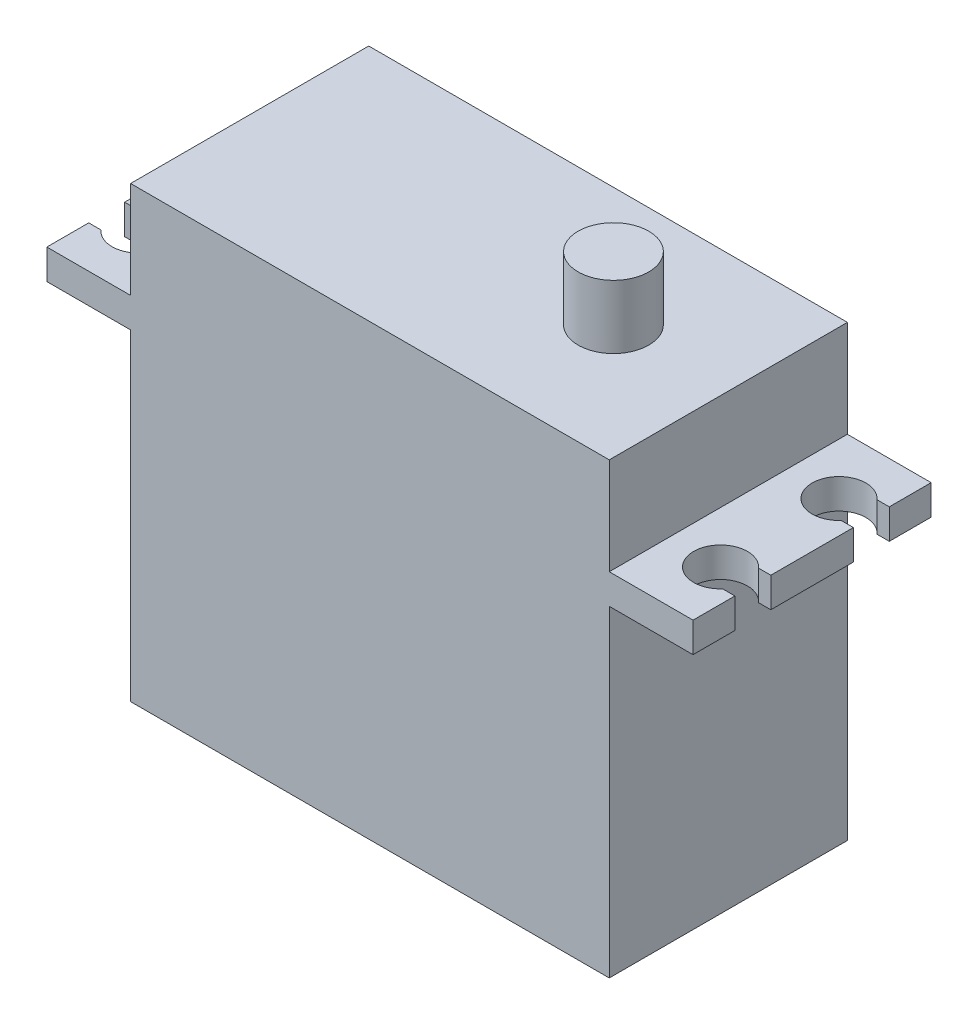
SolidWorks part; units mm, degrees
other "Body"
other "Axis"
material "Nylon 101"
ref_plane "Front Plane" through (0, 0, 0) normal (0, 0, 1) x (1, 0, 0)
ref_plane "Top Plane" through (0, 0, 0) normal (0, 1, 0) x (1, 0, 0)
ref_plane "Right Plane" through (0, 0, 0) normal (1, 0, 0) x (0, 0, -1)
sketch "Sketch1" plane through (0, 0, 0) normal (0, 1, 0) x (1, 0, 0)
  line L1 (-20, -9.95) -> (20, -9.95)
  line L2 (-20, -9.95) -> (-20, 9.95)
  line L3 (-20, 9.95) -> (20, 9.95)
  line L4 (20, -9.95) -> (20, 9.95)
  line L5 (-20, -9.95) -> (20, 9.95) construction
  line L6 (-20, 9.95) -> (20, -9.95) construction
  point P0 (0, 0)
  dimension "D1" = 40
  dimension "D2" = 19.9
extrude "Boss-Extrude1" add sketch "Sketch1" along normal blind 26.9
sketch "Sketch4" plane through (0, 26.9, 0) normal (0, 1, 0) x (1, 0, 0)
  line L0 (27, 6.45) -> (-27, 6.45) construction
  line L1 (-27, -9.95) -> (27, -9.95)
  line L2 (-27, -9.95) -> (-27, -6.45)
  line L3 (-27, 9.95) -> (27, 9.95)
  line L4 (27, -9.95) -> (27, -6.45)
  line L5 (-27, -9.95) -> (27, 9.95) construction
  line L6 (-27, 9.95) -> (27, -9.95) construction
  line L7 (-24.3, -4.95) -> (24.3, -4.95) construction
  line L8 (-24.3, -4.95) -> (-24.3, 4.95) construction
  line L9 (-24.3, 4.95) -> (24.3, 4.95) construction
  line L10 (24.3, -4.95) -> (24.3, 4.95) construction
  line L11 (-24.3, -4.95) -> (24.3, 4.95) construction
  line L12 (-24.3, 4.95) -> (24.3, -4.95) construction
  line L13 (-27, 3.45) -> (27, 3.45) construction
  line L14 (-27, -3.45) -> (27, -3.45) construction
  line L15 (-27, -6.45) -> (27, -6.45) construction
  line L16 (-25.9771, 6.45) -> (-27, 6.45)
  line L17 (-25.9771, 3.45) -> (-27, 3.45)
  line L18 (-25.9771, -3.45) -> (-27, -3.45)
  line L19 (-25.9771, -6.45) -> (-27, -6.45)
  line L20 (25.9771, 6.45) -> (27, 6.45)
  line L21 (25.9771, 3.45) -> (27, 3.45)
  line L22 (25.9771, -3.45) -> (27, -3.45)
  line L23 (25.9771, -6.45) -> (27, -6.45)
  line L24 (-27, -3.45) -> (-27, 3.45)
  line L25 (-27, 6.45) -> (-27, 9.95)
  line L26 (27, 6.45) -> (27, 9.95)
  line L27 (27, -3.45) -> (27, 3.45)
  arc A0 (25.9771, 6.45) -> (25.9771, 3.45) centre (24.3, 4.95) ccw
  arc A1 (25.9771, -3.45) -> (25.9771, -6.45) centre (24.3, -4.95) ccw
  arc A2 (-25.9771, 3.45) -> (-25.9771, 6.45) centre (-24.3, 4.95) ccw
  arc A3 (-25.9771, -6.45) -> (-25.9771, -3.45) centre (-24.3, -4.95) ccw
  point P0 (0, 0)
  point P14 (0, 0)
  dimension "D3" = 4.5
  dimension "D1" = 54
  dimension "D2" = 19.9
  dimension "D4" = 48.6
  dimension "D5" = 9.9
  dimension "D6" = 3
  dimension "D7" = 3
extrude "Boss-Extrude2" add sketch "Sketch4" along normal blind 2.5
sketch "Sketch5" plane through (0, 29.4, 0) normal (0, 1, 0) x (1, 0, 0)
  line L1 (-20, -9.95) -> (20, -9.95)
  line L2 (-20, -9.95) -> (-20, 9.95)
  line L3 (-20, 9.95) -> (20, 9.95)
  line L4 (20, -9.95) -> (20, 9.95)
  line L5 (-20, -9.95) -> (20, 9.95) construction
  line L6 (-20, 9.95) -> (20, -9.95) construction
  point P0 (0, 0)
extrude "Boss-Extrude3" add sketch "Sketch5" along normal blind 8.1
sketch "Sketch8" plane through (0, 0, 0) normal (0, 0, 1) x (1, 0, 0)
  line L0 (10.4, 42.8) -> (10.4, 3)
  line L1 (-20, 26.9) -> (-20, 0) construction
  line L2 (10.4, 42.8) -> (13.35, 42.8)
  line L3 (13.35, 42.8) -> (13.35, 25)
  line L4 (13.35, 25) -> (16.4, 25)
  line L5 (16.4, 25) -> (16.4, 3)
  line L6 (16.4, 3) -> (10.4, 3)
  dimension "D1" = 30.4
  dimension "D2" = 2.95
  dimension "D3" = 42.8
  dimension "D4" = 22
  dimension "D5" = 6
  dimension "D6" = 3
revolve "Cut-Revolve1" cut sketch "Sketch8" angle 360 about L0
revolve "Revolve1" add sketch "Sketch8<2>" angle 360 about L0
sketch "Sketch8<2>" plane through (0, 0, 0) normal (0, 0, 1) x (1, 0, 0) same geometry as "Sketch8"
